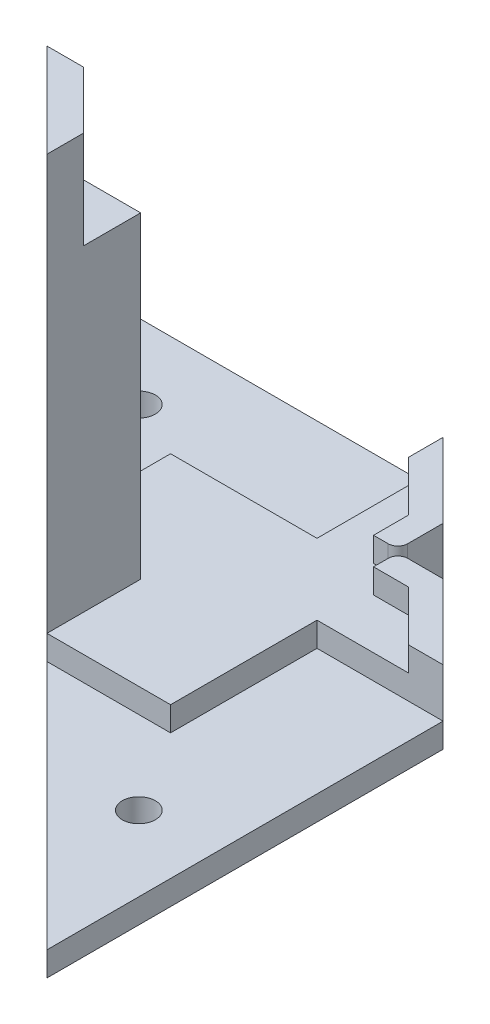
SolidWorks part; units mm, degrees
note: The reader was unsure of these and kept them because the rebuilt part matched: shared geometry of "Sketch2<3>".
ref_plane "Front Plane" through (0, 0, 0) normal (0, 0, 1) x (1, 0, 0)
ref_plane "Top Plane" through (0, 0, 0) normal (0, 1, 0) x (1, 0, 0)
ref_plane "Right Plane" through (0, 0, 0) normal (1, 0, 0) x (0, 0, -1)
sketch "Sketch1" plane through (0, 0, 0) normal (0, 1, 0) x (1, 0, 0)
  line L0 (28.7368, 28.7368) -> (34.9848, 28.7368)
  line L3 (0, 0) -> (28.7368, 28.7368)
  line L6 (34.9848, 28.7368) -> (44.6716, 19.05)
  line L7 (0, 0) -> (28.2726, 0)
  line L8 (28.2726, 0) -> (28.2726, 19.05)
  line L9 (28.2726, 19.05) -> (44.6716, 19.05)
  point P1 (0, 0)
  point P7 (0, 0)
  point P9 (28.2726, 19.05)
  point P10 (0, 0)
  point P11 (0, 0)
  dimension "D1" = 135
  dimension "D2" = 225
  dimension "D3" = 40.64
  dimension "D5" = 90
extrude "Boss-Extrude1" add sketch "Sketch1" along normal blind 3.175
mirror "Mirror1" about plane through (0, 3.175, 0) normal (-0.7071, 0, -0.7071) of "Boss-Extrude1"
sketch "Sketch2" plane through (0, 3.175, 0) normal (0, 1, 0) x (1, 0, 0)
  line L0 (29.115, 25.5618) -> (29.115, 28.7368)
  line L2 (33.6697, 25.5618) -> (40.1815, 19.05)
  line L3 (28.2726, 19.05) -> (44.6716, 19.05) construction
  line L4 (34.9848, 28.7368) -> (44.6716, 19.05) construction
  line L5 (29.115, 25.5618) -> (33.6697, 25.5618)
  line L6 (34.9848, 28.7368) -> (44.6716, 19.05)
  line L9 (28.7368, 28.7368) -> (34.9848, 28.7368) construction
  line L16 (44.6716, 19.05) -> (40.1815, 19.05)
  line L18 (34.9848, 28.7368) -> (29.115, 28.7368)
  line L19 (28.7368, 28.7368) -> (0, 0) construction
  line L21 (0, 0) -> (28.2726, 0) construction
  line L22 (12.192, 12.192) -> (12.192, 0)
  line L23 (12.192, 0) -> (6.096, 6.096)
  line L24 (6.096, 6.096) -> (12.192, 12.192)
  point P2 (7.811, 7.811)
  point P12 (0, 0)
  point P15 (11.1366, 11.1366)
  point P19 (12.192, 12.192)
  point P20 (6.3935, 6.3935)
  point P22 (7.7019, 0)
  point P24 (0, 0)
  point P28 (0, 0)
  point P32 (0, 0)
  point P33 (12.192, 4.4912)
  point P34 (12.192, 4.4901)
  point P35 (12.192, 12.192)
  point P36 (11.904, 11.904)
  dimension "D1" = 3.175
  dimension "D2" = 3.175
  dimension "D4" = 12.192
extrude "Boss-Extrude2" add sketch "Sketch2" along normal blind 3.175 contours L5 L2 L16 L6 L18 L0
ref_plane "Plane1" through (0, 0, 0) normal (0.7071, 0, 0.7071) x (0.7071, 0, -0.7071)
fillet "Fillet1" radius 1.27 1 edges at (29.115, 4.7625, -28.7368)
extrude "Boss-Extrude3" add sketch "Sketch2<3>" along normal blind 41.275
sketch "Sketch2<3>" plane through (0, 3.175, 0) normal (0, 1, 0) x (1, 0, 0) same geometry as "Sketch2"
mirror "Mirror2" about plane through (0, 0, 0) normal (0.7071, 0, 0.7071) of "Boss-Extrude3", "Boss-Extrude2", "Fillet1"
sketch "Sketch4" plane through (0, 44.45, 0) normal (0, 1, 0) x (1, 0, 0)
  line L0 (12.192, 0) -> (0, 12.192)
  line L1 (0, 12.192) -> (4.7625, 12.192)
  line L2 (12.192, 12.192) -> (0, 12.192) construction
  line L3 (4.7625, 12.192) -> (12.192, 4.7625)
  line L4 (12.192, 12.192) -> (12.192, 0) construction
  line L5 (12.192, 4.7625) -> (12.192, 0)
  dimension "D1" = 4.7625
extrude "Boss-Extrude4" add sketch "Sketch4" along normal blind 12.7
hole_wizard "#18 (0.1695) Diameter Hole1" positions "Sketch5" profile "Sketch6" hole size "#18" standard "ANSI Inch" end condition through all
sketch "Sketch5" plane through (8.4773, 0, -8.4772) normal (0.7071, 0, -0.7071) x (-0.7071, 0, -0.7071)
  line L0 (-5.2534, 57.15) -> (5.2534, 57.15) construction
  point P0 (0, 52.3875)
  dimension "D1" = 4.7625
sketch "Sketch6" plane through (8.4773, 52.3875, -8.4772) normal (0, 1, 0) x (-0.7071, 0, -0.7071)
  line L0 (0, 0) -> (0, 11.9886)
  line L1 (0, 11.9886) -> (2.1526, 11.9886)
  line L2 (2.1526, 11.9886) -> (2.1526, 0)
  line L5 (2.1526, 0) -> (0, 0)
  line L11 (0, -6.35) -> (0, 107.95) construction
  dimension "Thru Hole Dia." = 4.3053
  dimension "Thru Hole Depth" = 11.9886
sketch "Sketch7" plane through (0, 3.175, 0) normal (0, 1, 0) x (1, 0, 0)
  line L0 (0, 0) -> (12.192, 0)
  line L1 (12.192, 0) -> (0, 12.192)
  line L2 (0, 12.192) -> (0, 0)
extrude "Cut-Extrude1" cut sketch "Sketch7" against normal blind 9.525
sketch "Sketch8" plane through (0, 0, 0) normal (0, -1, 0) x (-1, 0, 0)
  line L0 (-6.096, 6.096) -> (32.4796, 44.6716)
  line L2 (-6.096, 6.096) -> (-28.7368, 28.7368)
  line L3 (-1.2348, 1.2348) -> (1.2348, -1.2348) construction
  line L4 (-28.7368, 28.7368) -> (-34.9848, 28.7368) construction
  line L5 (-28.7368, 28.7368) -> (-28.7368, 34.9848)
  line L6 (-28.7368, 34.9848) -> (-19.05, 44.6716) construction
  line L7 (-28.7368, 28.7368) -> (-28.7368, 34.9848) construction
  line L8 (-28.7368, 34.9848) -> (-19.05, 44.6716)
  line L9 (32.4796, 44.6716) -> (-19.05, 44.6716)
  point P1 (-6.096, 6.096)
  point P2 (-19.05, 44.6716)
  point P3 (-19.05, 44.6716)
extrude "Boss-Extrude5" add sketch "Sketch8" along normal blind 3.175
mirror "Mirror3" about plane through (0, 0, 0) normal (0.7071, 0, 0.7071) of "Boss-Extrude5"
hole_wizard "#18 (0.1695) Diameter Hole2" positions "Sketch9" profile "Sketch10" hole size "#18" standard "ANSI Inch" end condition through all
sketch "Sketch9" plane through (0, -3.175, 0) normal (0, -1, 0) x (-1, 0, 0)
  line L1 (-44.6716, -32.4796) -> (-44.6716, 19.05) construction
  point P0 (-34.925, -10.7782)
  dimension "D1" = 9.7466
sketch "Sketch10" plane through (34.925, -3.175, 10.7782) normal (1, 0, 0) x (0, 0, -1)
  line L0 (0, 0) -> (0, 60.325)
  line L1 (0, 60.325) -> (2.1526, 60.325)
  line L2 (2.1526, 60.325) -> (2.1526, 0)
  line L5 (2.1526, 0) -> (0, 0)
  line L11 (0, -6.35) -> (0, 107.95) construction
  dimension "Thru Hole Dia." = 4.3053
  dimension "Thru Hole Depth" = 60.325
mirror "Mirror4" about plane through (0, 0, 0) normal (0.7071, 0, 0.7071) of "#18 (0.1695) Diameter Hole2"
